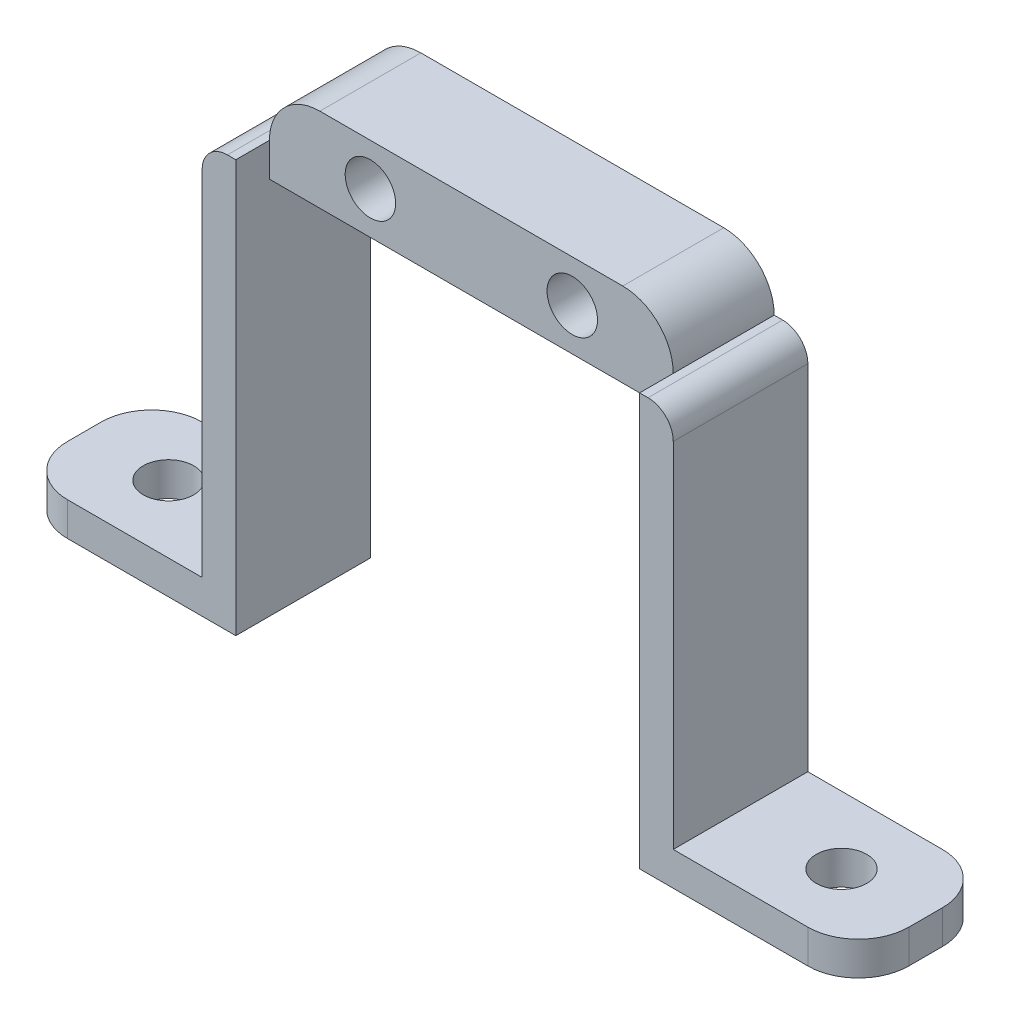
SolidWorks part; units mm, degrees
ref_plane "Alzado" through (0, 0, 0) normal (0, 0, 1) x (1, 0, 0)
ref_plane "Planta" through (0, 0, 0) normal (0, 1, 0) x (1, 0, 0)
ref_plane "Vista lateral" through (0, 0, 0) normal (1, 0, 0) x (0, 0, -1)
sketch "Croquis1" plane through (0, 0, 0) normal (0, 0, 1) x (1, 0, 0)
  line L0 (0, 0) -> (13, 0)
  line L1 (13, 0) -> (13, 22.5)
  line L2 (13, 22.5) -> (37, 22.5)
  line L3 (37, 22.5) -> (37, 0)
  line L4 (37, 0) -> (50, 0)
  line L5 (25, 22.5) -> (25, 0) construction
  dimension "D1" = 25
  dimension "D2" = 24
  dimension "D4" = 22.5
extrude "Extruir-Lámina1" add sketch "Croquis1" along normal blind 8 thin thin type one direction reverse wall 2
sketch "Croquis2" plane through (0, 0, 8) normal (0, 0, 1) x (1, 0, 0)
  line L0 (11, 24.5) -> (39, 24.5) construction
  line L1 (13, 22.5) -> (37, 22.5)
  line L2 (13, 22.5) -> (13, 24.5)
  line L3 (13, 24.5) -> (37, 24.5)
  line L4 (37, 22.5) -> (37, 24.5)
  point P7 (37, 22.5)
extrude "Cortar-Extruir1" cut sketch "Croquis2" against normal blind 2
sketch "Croquis3" plane through (0, 24.5, 0) normal (0, 1, 0) x (1, 0, 0)
  line L1 (13, -6) -> (37, -6)
  line L2 (13, -6) -> (13, 0)
  line L3 (13, 0) -> (37, 0)
  line L4 (37, -6) -> (37, 0)
  point P5 (37, -6)
  dimension "D1" = 6
extrude "Saliente-Extruir1" add sketch "Croquis3" along normal blind 3
sketch "Croquis4" plane through (0, 0, 0) normal (0, 0, -1) x (-1, 0, 0)
  line L1 (-37, 27.5) -> (-13, 27.5) construction
  circle A0 centre (-19, 25) radius 1.5
  circle A1 centre (-31, 25) radius 1.5
  point P0 (-25, 27.5)
  point P6 (-13.5, 27.5)
  dimension "D2" = 3
  dimension "D1" = 6
  dimension "D3" = 2.5
  dimension "D4" = 12
extrude "Cortar-Extruir2" cut sketch "Croquis4" against normal through all
sketch "Croquis5" plane through (0, 0, 0) normal (0, -1, 0) x (1, 0, 0)
  line L0 (39, 8) -> (50, 8) construction
  line L3 (25, 6) -> (25, 0) construction
  line L4 (13, 6) -> (37, 6) construction
  line L5 (13, 0) -> (37, 0) construction
  line L6 (39, 8) -> (50, 8) construction
  circle A0 centre (45, 4) radius 1.5
  circle A1 centre (5, 4) radius 1.5
  dimension "D2" = 3
  dimension "D1" = 4
  dimension "D3" = 20
extrude "Cortar-Extruir3" cut sketch "Croquis5" against normal through all
fillet "Redondeo1" radius 3 6 edges at (13, 27.5, 3) (37, 27.5, 3) (50, 1, 8) (50, 1, 0) (0, 1, 0) (0, 1, 8)
fillet "Redondeo2" radius 1.5 2 edges at (39, 24.5, 4) (11, 24.5, 4)
